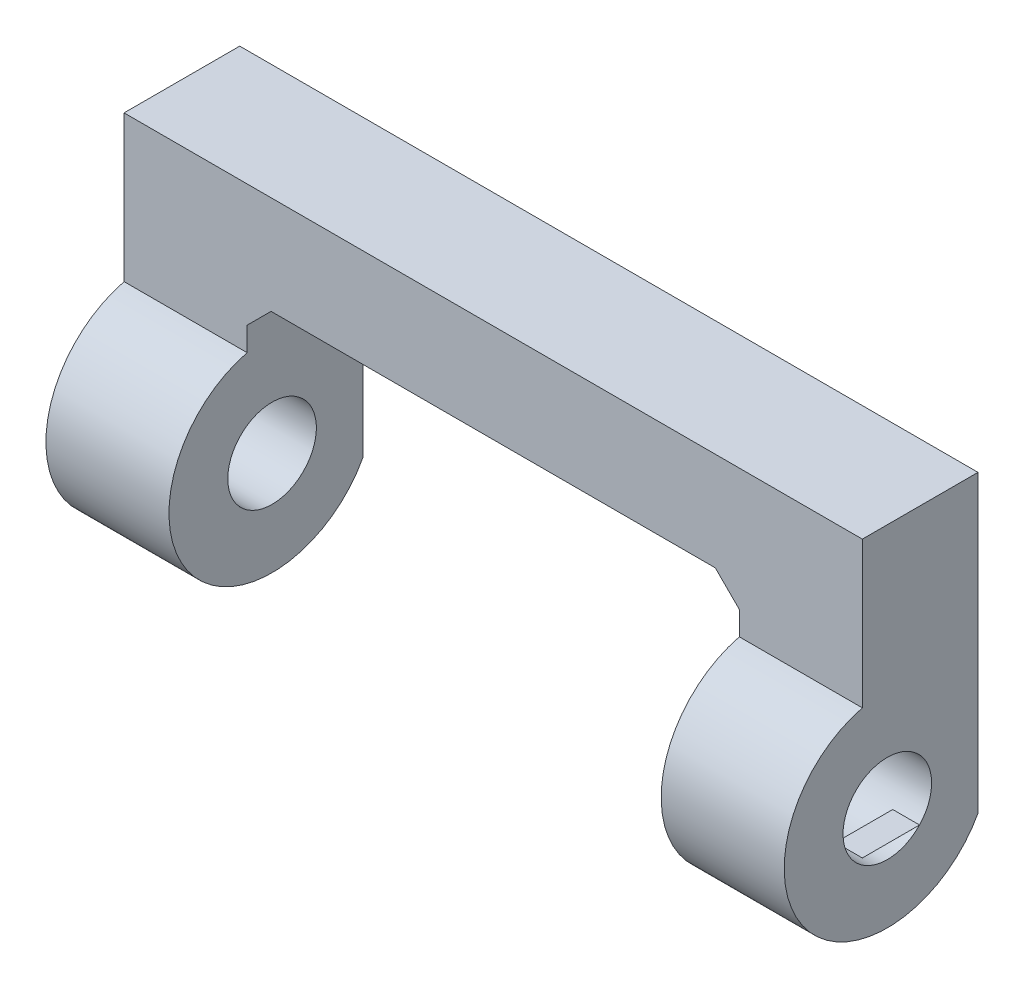
SolidWorks part; units mm, degrees
ref_plane "Front Plane" through (0, 0, 0) normal (0, 0, 1) x (1, 0, 0)
ref_plane "Top Plane" through (0, 0, 0) normal (0, 1, 0) x (1, 0, 0)
ref_plane "Right Plane" through (0, 0, 0) normal (1, 0, 0) x (0, 0, -1)
sketch "Model" plane through (0, 0, 0) normal (0, 0, 1) x (1, 0, 0)
  line L0 (289.64, 39.2394) -> (289.64, 28.0169)
  line L1 (319.644, 39.2394) -> (319.644, 28.0165)
  line L2 (289.64, 39.2394) -> (319.644, 39.2394)
  line L3 (314.644, 28.0181) -> (319.644, 28.0165)
  line L4 (314.644, 34.2647) -> (314.644, 28.0181)
  line L11 (313.6697, 35.2359) -> (314.644, 34.2647)
  line L12 (313.6697, 35.2359) -> (314.644, 34.2634)
  line L18 (313.6697, 35.2359) -> (313.6677, 35.2391)
  line L19 (314.644, 34.2647) -> (313.6677, 35.2391)
  line L21 (289.64, 28.0169) -> (294.64, 28.0201)
  line L24 (294.64, 28.0201) -> (294.64, 34.2666)
  line L32 (294.64, 34.2666) -> (295.6145, 35.2409)
  line L33 (295.6125, 35.2377) -> (295.6145, 35.2409)
  line L34 (295.6125, 35.2377) -> (294.64, 34.2666)
  line L36 (304.6401, 35.24) -> (313.6677, 35.2391)
  line L37 (304.6401, 35.24) -> (313.6697, 35.2359)
  line L44 (295.6145, 35.2409) -> (304.6401, 35.24)
  line L45 (295.6125, 35.2377) -> (304.6401, 35.24)
  line L48 (304.6401, 35.24) -> (304.6401, 35.2368)
  line L49 (295.6125, 35.2377) -> (304.6401, 35.2368)
  line L53 (304.6401, 35.2368) -> (313.6697, 35.2359)
  dimension "D1" = 5
  dimension "D2" = 5
extrude "Boss-Extrude1" add sketch "Model" along normal blind 5 contours L32 L44 L36 L19 L4 L3 L1 L2 L0 L21 L24 region at (304.642, 38.9191, 0)
sketch "Sketch2" plane through (289.64, 0, 0) normal (-1, 0, 0) x (0, 0, 1)
  line L0 (0, 30.5265) -> (0, 27.9427)
  arc A0 (0, 27.9427) -> (0, 30.5265) centre (3.9858, 29.2346) ccw
  circle A1 centre (3.9857, 29.252) radius 1.7997
  line M218 (0, 28.0169) -> (5, 28.0169)
  line M219 (5, 28.0169) -> (5, 39.2394)
extrude "Cut-Extrude1" cut sketch "Sketch2" against normal through all contours A1 M219 M218 region at (289.64, 29.443, 3.7016)
extrude "Boss-Extrude2" add sketch "Sketch2<3>" against normal blind 5
sketch "Sketch2<3>" plane through (289.64, 0, 0) normal (-1, 0, 0) x (0, 0, 1) same geometry as "Sketch2"
ref_plane "Plane1" through (304.642, 0, 0) normal (-1, 0, 0) x (0, 0, 1)
sketch "Sketch3" plane through (314.644, 0, 0) normal (-1, 0, 0) x (0, 0, 1)
  line L0 (0, 30.5265) -> (0, 27.9427)
  arc A0 (0, 27.9427) -> (0, 30.5265) centre (3.9858, 29.2346) ccw
  circle A1 centre (3.9857, 29.252) radius 1.7997
  point P0 (3.9858, 29.2346)
extrude "Boss-Extrude3" add sketch "Sketch3" against normal blind 5
chamfer "Chamfer1" distance 0.3 angle 45 9 edges at (314.644, 31.1037, 0) (314.1558, 34.7519, 0) (309.1539, 35.2396, 0) (300.1273, 35.2405, 0) (295.1272, 34.7538, 0) (294.64, 31.1047, 0) (289.64, 33.5911, 0) (304.642, 39.2394, 0) (319.644, 33.5911, 0)
fillet "Fillet1" radius 0.4 2 edges at (317.144, 27.9427, 0) (292.14, 27.9427, 0)
